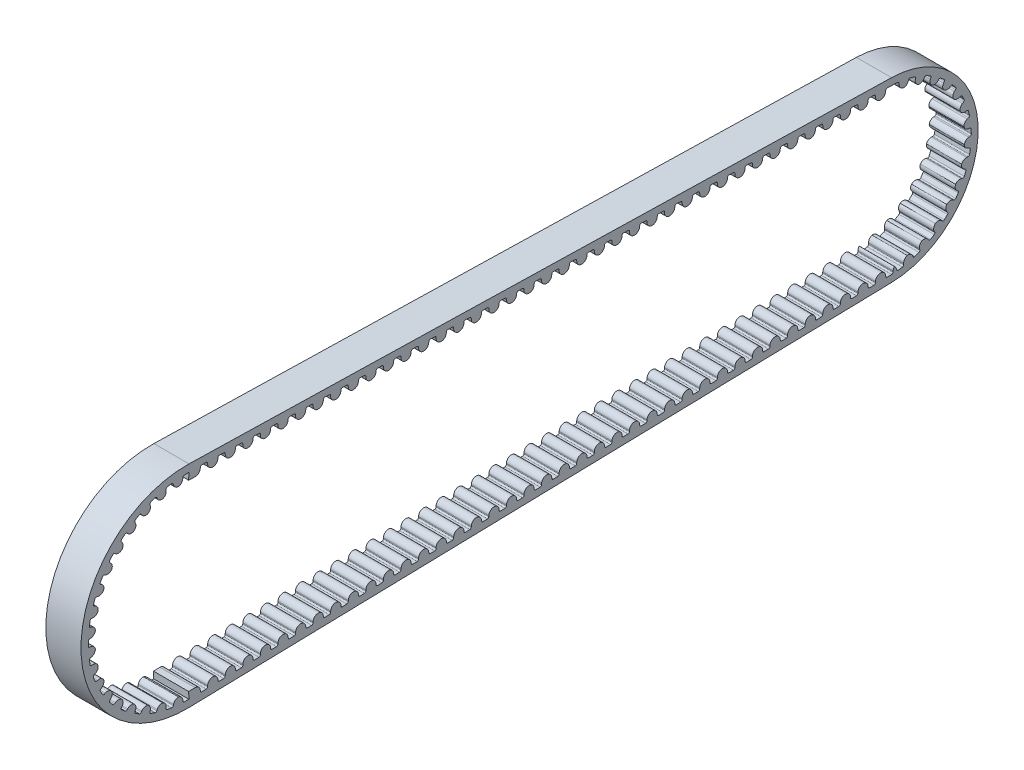
SolidWorks part; units mm, degrees
material "蒸气橡胶软管"
ref_plane "前视基准面" through (0, 0, 0) normal (0, 0, 1) x (1, 0, 0)
ref_plane "上视基准面" through (0, 0, 0) normal (0, 1, 0) x (1, 0, 0)
ref_plane "右视基准面" through (0, 0, 0) normal (1, 0, 0) x (0, 0, -1)
sketch "草图1" plane through (0, 0, 0) normal (1, 0, 0) x (0, 0, -1)
  line L0 (0.4301, 18.0039) -> (120.3217, 15.1397)
  line L1 (0.4301, -18.0039) -> (120.3217, -15.1397)
  line L2 (0, 0) -> (119.96, 0) construction
  line L3 (0, 0) -> (-363.6995, 0) construction
  line L4 (0, 0) -> (0.4301, 18.0039) construction
  arc A0 (0.4301, 18.0039) -> (0.4301, -18.0039) centre (0, 0) ccw
  arc A1 (120.3217, -15.1397) -> (120.3217, 15.1397) centre (119.96, 0) ccw
  dimension "d2" = 18.009
  dimension "d1" = 15.144
  dimension "dist" = 119.96
  dimension "Angle" = 91.369
sketch "草图2" plane through (0, 0, 0) normal (0, 0, 1) x (1, 0, 0)
  line L0 (-3, 18.009) -> (3, 18.009)
  line L1 (3, 18.009) -> (3, 15.609)
  line L2 (3, 15.609) -> (-3, 15.609)
  line L3 (-3, 15.609) -> (-3, 18.009)
  line L4 (0, 15.609) -> (0, 18.009) construction
  line L5 (0, -18.009) -> (0, 18.009) construction
  dimension "bs" = 6
  dimension "hs" = 2.4
sweep "扫描1" add profiles "草图2" path "草图1"
ref_axis "基准轴1" through (-33.0003, 0, 0) along (1, 0, 0)
ref_plane "基准面1" through (0, 0, -119.96) normal (0, 0, 1) x (1, 0, 0)
ref_axis "基准轴2" through (-33.0001, 0, -119.96) along (1, 0, 0)
sketch "草图3" plane through (3, 0, 0) normal (1, 0, 0) x (0, 0, -1)
  line L0 (0, 0) -> (-284.3079, 0) construction
  line L1 (-16.7606, -0.3825) -> (-16.7606, 0.3825)
  line L2 (-16.5334, 0.6222) -> (-16.364, 0.6312)
  line L3 (-15.5406, 1.5) -> (-13.1202, 1.5)
  line L4 (-13.1202, 1.5) -> (-13.1202, -1.5)
  line L5 (-15.5406, -1.5) -> (-13.1202, -1.5)
  line L6 (-16.5334, -0.6222) -> (-16.364, -0.6312)
  arc A0 (-16.5334, 0.6222) -> (-16.7606, 0.3825) centre (-16.5206, 0.3825) ccw
  arc A2 (-16.364, 0.6312) -> (-15.5406, 1.5) centre (-16.4106, 1.5) ccw
  arc A3 (0.3728, 15.6045) -> (0.3728, -15.6045) centre (0, 0) ccw construction
  arc A4 (-16.364, -0.6312) -> (-15.5406, -1.5) centre (-16.4106, -1.5) cw
  arc A5 (-16.5334, -0.6222) -> (-16.7606, -0.3825) centre (-16.5206, -0.3825) cw
  point P9 (-282.5279, 0)
  point P14 (-16.7606, 0)
  point P15 (-16.7606, 0.61)
  point P23 (-13.1202, 0)
  point P24 (-283.0879, 0)
  dimension "ra" = 0.87
  dimension "rr" = 0.24
  dimension "D4" = 1.22
  dimension "D3" = 2.4204
  dimension "PbS" = 1.22
  dimension "angle" = 6.134
  dimension "ht" = 1.22
  dimension "Pb" = 3
  dimension "S" = 1.78
extrude "切除-拉伸1" cut sketch "草图3" against normal through all
pattern_circular "阵列(圆周)1" count 36 over 360 about axis through (-33.0003, 0, 0) along (1, 0, 0) of "切除-拉伸1"
sketch "草图4" plane through (3, 0, 0) normal (1, 0, 0) x (0, 0, -1)
  line L0 (119.96, 0) -> (135.0978, 0.434) construction
  line L1 (133.9077, 0.77) -> (133.9289, 0.0303)
  line L2 (132.7418, -1.1342) -> (131.7422, -1.1628) construction
  line L3 (131.7422, -1.1628) -> (131.6562, 1.8359)
  line L4 (133.7232, -0.2141) -> (133.4871, -0.2481)
  line L5 (133.6884, 1.0023) -> (133.4507, 1.0228)
  line L6 (132.6558, 1.8646) -> (131.6562, 1.8359) construction
  line L7 (131.7422, -1.1628) -> (131.7668, -2.0227)
  line L8 (131.6562, 1.8359) -> (131.6315, 2.6958)
  line L9 (0, 0) -> (119.96, 0) construction
  line L10 (119.96, 0) -> (135.104, 0) construction
  arc A0 (133.4871, -0.2481) -> (132.7418, -1.1342) centre (133.6114, -1.1092) ccw
  arc A2 (132.7418, -1.1342) -> (131.7668, -2.0227) centre (131.8721, -1.1591) cw
  arc A3 (133.7232, -0.2141) -> (133.9289, 0.0303) centre (133.689, 0.0235) ccw
  arc A4 (133.6884, 1.0023) -> (133.9077, 0.77) centre (133.6678, 0.7632) cw
  arc A5 (133.4507, 1.0228) -> (132.6558, 1.8646) centre (133.5254, 1.8895) cw
  arc A6 (132.6558, 1.8646) -> (131.6315, 2.6958) centre (131.7861, 1.8397) ccw
  point P0 (119.96, 0)
  point P15 (133.9183, 0.4002)
  point P17 (133.935, -0.1835)
  point P25 (131.6992, 0.3366)
  dimension "D1" = 0.74
  dimension "D4" = 1
  dimension "D5" = 0.87
  dimension "D6" = 0.24
  dimension "D8" = 0.87
  dimension "D2" = 3
  dimension "D3" = 1.22
  dimension "D7" = 1.18
  dimension "D9" = 135.104
  dimension "D10" = 1.642
  dimension "D11" = 15.144
extrude "切除-拉伸2" cut sketch "草图4" against normal through all
pattern_circular "阵列(圆周)2" count 30 over 360 about axis through (-33.0001, 0, -119.96) along (1, 0, 0) of "切除-拉伸2"
sketch "草图11" plane through (0, 18.0039, -0.4301) normal (0, 0.9997, -0.0239) x (1, 0, 0)
  line L1 (-3, 119.9258) -> (3, 119.9258)
  line L2 (-3, 119.9258) -> (-3, 0)
  line L3 (-3, 0) -> (3, 0)
  line L4 (3, 119.9258) -> (3, 0)
extrude "拉伸11" add sketch "草图11" against normal blind 2.4
mirror "镜向2" about plane through (0, 0, 0) normal (0, 1, 0) of "拉伸11"
sketch "草图5" plane through (3, 0, 0) normal (1, 0, 0) x (0, 0, -1)
  line L0 (0, 0) -> (0.4019, 16.8242) construction
  line L1 (0.4019, 16.8242) -> (2.9906, 16.7624) construction
  line L2 (2.9906, 16.7624) -> (2.5887, -0.0618) construction
  line L3 (2.5887, -0.0618) -> (0, 0) construction
  line L4 (2.6082, 16.7715) -> (3.373, 16.7532)
  line L5 (3.6072, 16.5204) -> (3.6122, 16.3508)
  line L6 (8.9455, 203.2189) -> (4.4611, 15.5069) construction
  line L7 (4.4611, 15.5069) -> (4.4133, 13.5075)
  line L8 (4.4133, 13.5075) -> (1.4142, 13.5791)
  line L9 (5.9463, 203.2906) -> (1.4619, 15.5785) construction
  line L10 (1.4619, 15.5785) -> (1.4142, 13.5791)
  line L11 (2.3632, 16.5501) -> (2.3501, 16.381)
  line L12 (0.4019, 16.8242) -> (0.8796, 36.8185) construction
  arc A0 (3.6122, 16.3508) -> (4.4611, 15.5069) centre (4.4818, 16.3766) ccw
  arc A1 (3.6072, 16.5204) -> (3.373, 16.7532) centre (3.3673, 16.5133) ccw
  arc A2 (2.3632, 16.5501) -> (2.6082, 16.7715) centre (2.6025, 16.5316) cw
  arc A3 (2.3501, 16.381) -> (1.4619, 15.5785) centre (1.4827, 16.4483) cw
  point P2 (2.3808, 16.7769)
  point P13 (2.9906, 16.7624)
  point P14 (3.6005, 16.7478)
  point P23 (2.9137, 13.5433)
  dimension "D3" = 0.87
  dimension "D4" = 1.22
  dimension "D5" = 2
  dimension "D6" = 0.24
  dimension "D1" = 1.22
  dimension "D2" = 3
  dimension "D8" = 20
  dimension "D9" = 16.829
  dimension "D22" = 2.5894
extrude "切除-拉伸3" cut sketch "草图5" against normal up to next
pattern_linear "阵列(线性)1" count 40 along (0, -0.0239, -0.9997) of "切除-拉伸3"
mirror "镜向1" about plane through (0, 0, 0) normal (0, 1, 0) of "阵列(线性)1", "切除-拉伸3"
equation "\"D1@基准面1\" = \"dist@草图1\""
equation "\"D3@草图4\" =\"D4@草图3\""
equation "\"D5@草图4\" =\"ra@草图3\""
equation "\"D6@草图4\" =\"rr@草图3\""
equation "\"D1@阵列(线性)1\" = \"RD1@注解\" / \"Pb@阵列(线性)1\"  "
equation "\"D3@草图5\" = \"ra@草图3\""
equation "\"D4@草图5\" = \"D4@草图3\""
equation "\"D6@草图5\" = \"rr@草图3\""
equation "\"D9@草图5\" =\"d2@草图1\" - \"hs@草图2\" + \"ht@草图3\""
equation "\"D1@草图5\" = \"PbS@草图3\""
equation "\"D4@草图3\" = \"ht@草图3\""
equation "\"D2@草图4\" = \"Pb@草图3\""
equation "\"D2@草图5\" = \"Pb@草图3\""
equation "\"PbS@草图3\" = \"Pb@草图3\" - \"S@草图3\""
equation "\"D7@草图4\" = \"hs@草图2\" - \"ht@草图3\""
equation "\"D8@草图4\" = \"D5@草图4\" "
equation "\"D9@草图4\" = \"dist@草图1\" + \"d1@草图1\""
equation "\"D1@拉伸11\" = \"hs@草图2\""
equation "\"D1@草图4\" = \"PbS@草图3\" - \"rr@草图3\" - \"rr@草图3\""
equation "\"D11@草图4\" = \"D9@草图4\" - \"dist@草图1\""
